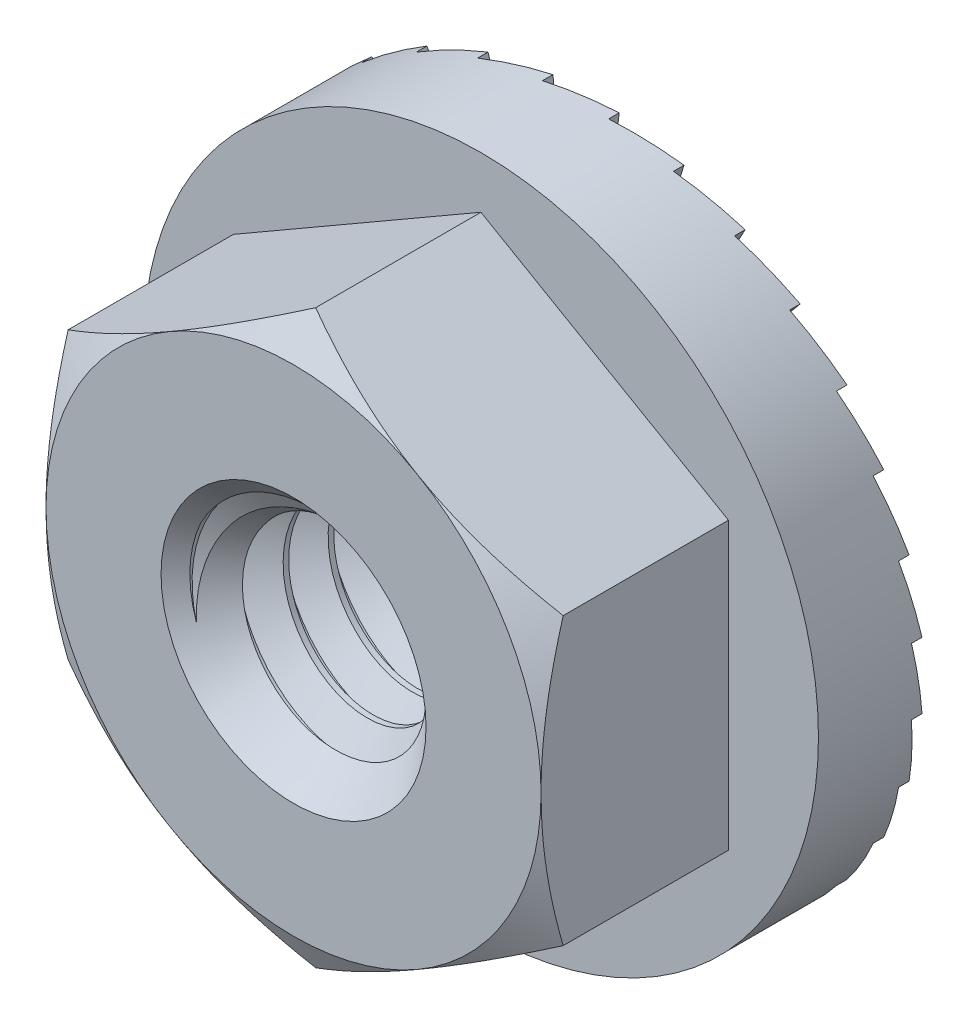
SolidWorks part; units mm, degrees
ref_plane "Front Plane" through (0, 0, 0) normal (0, 0, 1) x (1, 0, 0)
ref_plane "Top Plane" through (0, 0, 0) normal (0, 1, 0) x (1, 0, 0)
ref_plane "Right Plane" through (0, 0, 0) normal (1, 0, 0) x (0, 0, -1)
sketch "Sketch1" plane through (0, 0, 0) normal (0, 0, 1) x (1, 0, 0)
  line L1 (0, 5.041) -> (-4.3656, 2.5205)
  line L2 (-4.3656, 2.5205) -> (-4.3656, -2.5205)
  line L3 (-4.3656, -2.5205) -> (0, -5.041)
  line L4 (0, -5.041) -> (4.3656, -2.5205)
  line L5 (4.3656, -2.5205) -> (4.3656, 2.5205)
  line L6 (4.3656, 2.5205) -> (0, 5.041)
  circle A0 centre (0, 0) radius 4.3656 construction
  dimension "Hex" = 8.7312
extrude "Extrude1" add sketch "Sketch1" against normal blind 5.1594
sketch "Sketch13" plane through (0, 0, -5.1594) normal (0, 0, -1) x (-1, 0, 0)
  circle A0 centre (0, 0) radius 5.9531
  dimension "Flange od" = 11.9062
extrude "Extrude3" add sketch "Sketch13" against normal blind 1.8542
sketch "Sketch2" plane through (0, 0, 0) normal (0, 0, 1) x (1, 0, 0)
  circle A0 centre (0, 0) radius 4.3656 construction
  circle A1 centre (0, 0) radius 4.3656
extrude "Cut-Extrude1" cut sketch "Sketch2" against normal through all draft 60 flip side to cut
sketch "Sketch4" plane through (0, 0, 0) normal (0, 0, 1) x (1, 0, 0)
  circle A0 centre (0, 0) radius 2.0828
  dimension "Thread Dia" = 4.1656
extrude "Cut-Extrude3" cut sketch "Sketch4" against normal through all
sketch "Sketch7" plane through (0, 0, 0) normal (0, 0, 1) x (1, 0, 0)
  circle A4 centre (0, 0) radius 2.3368
  circle A5 centre (0, 0) radius 2.3368
  dimension "D1" = 0.254
sketch "Sketch8" plane through (0, 0, -5.1594) normal (0, 0, -1) x (-1, 0, 0)
  circle A1 centre (0, 0) radius 2.3368
  circle A2 centre (0, 0) radius 2.3368 construction
sketch "Sketch5" plane through (0, 0, 0) normal (0, 0, 1) x (1, 0, 0)
  circle A0 centre (0, 0) radius 2.0828 construction
  circle A1 centre (0, 0) radius 2.0828
curve "Helix/Spiral1" pitch 0.7937 height 5.9531 turns 7.5 parameters "pitch"=0.7937
sketch "Sketch9" plane through (0, 0, 0) normal (1, 0, 0) x (0, 0, -1)
  line L0 (-0.3969, 2.0828) -> (-0.2977, 2.0828)
  line L1 (-0.2977, 2.0828) -> (0, 1.5672)
  line L2 (-0.3969, 2.0828) -> (-0.6945, 1.5672)
  line L3 (-0.6945, 1.5672) -> (0, 1.5672)
  line L4 (-0.3473, 2.0828) -> (-0.3473, 1.5672) construction
  line L5 (-0.5457, 1.825) -> (-0.1488, 1.825) construction
  line L7 (0, 1.5672) -> (0, 2.0828) construction
  line L8 (0, 2.0828) -> (0, -2.0828) construction
  dimension "D1" = 0.0992
  dimension "D2" = 0.3969
  dimension "D3" = 60
sketch "Sketch12" plane through (0, 0, 0) normal (0, 0, 1) x (1, 0, 0)
  circle A0 centre (0, 0) radius 1.5672
  circle A1 centre (0, 0) radius 2.0828 construction
  circle A2 centre (0, 0) radius 2.0828
extrude "Extrude2" add sketch "Sketch12" against normal up to surface (5.1594 mm away)
sweep "Cut-Sweep1" cut profiles "Sketch9" path "Helix/Spiral1"
extrude "Cut-Extrude6" cut sketch "Sketch7" against normal through all draft 45
extrude "Cut-Extrude7" cut sketch "Sketch8" against normal through all draft 45
sketch "Sketch14" plane through (0, 0, -5.1594) normal (0, 0, -1) x (-1, 0, 0)
  circle A4 centre (0, 0) radius 4.3688
  circle A5 centre (0, 0) radius 4.3688
  dimension "D1" = 2.032
extrude "Cut-Extrude8" cut sketch "Sketch14" against normal blind 0.1854 flip side to cut
sketch "Sketch15" plane through (0, 0, -4.974) normal (0, 0, -1) x (-1, 0, 0)
  line L0 (-0.4282, 4.3478) -> (-0.5835, 5.9245)
  line L1 (0.4282, 4.3478) -> (0.5835, 5.9245)
  line L2 (0, 0) -> (0.4282, 4.3478) construction
  line L3 (0, 0) -> (-0.4282, 4.3478) construction
  circle A0 centre (0, 0) radius 5.9531 construction
  circle A1 centre (0, 0) radius 4.3688 construction
  arc A2 (0.5835, 5.9245) -> (-0.5835, 5.9245) centre (0, 0) ccw
  arc A3 (0.4282, 4.3478) -> (-0.4282, 4.3478) centre (0, 0) ccw
  dimension "D1" = 11.25
extrude "Extrude4" add sketch "Sketch15" along normal up to surface (0.1854 mm away) separate body up to face at (-2.3368, 0, -5.1594)
sketch "Sketch16" plane through (0, 0, 0) normal (0, 1, 0) x (1, 0, 0)
  line L0 (-0.5835, 4.974) -> (0.5835, 5.1594)
  line L4 (-0.5835, 4.974) -> (0.5835, 4.974)
  line L5 (0.5835, 4.974) -> (0.5835, 5.1594)
  line L6 (0.5835, 5.1594) -> (-0.5835, 5.1594)
  line L7 (-0.5835, 5.1594) -> (-0.5835, 4.974)
  line L8 (-0.5835, 4.974) -> (0.5835, 4.974) construction
  line L9 (0.5835, 4.974) -> (0.5835, 5.1594) construction
  line L10 (0.5835, 5.1594) -> (-0.5835, 5.1594)
  line L11 (-0.5835, 5.1594) -> (-0.5835, 4.974)
  dimension "D1" = 0
extrude "Cut-Extrude9" cut sketch "Sketch16" along normal through all
pattern_circular "CirPattern1" count 32 over 360 about axis through (0, 0, 0) along (0, 0, 1) of bodies 119
combine bodies "Combine1" operation type add bodies to combine 117 119 120 121 122 123 124 125 126 127 128 129 130 131 132 133 134 135 136 137 139 140 141 142 143 144 145 146 147 148 149 150 151
sketch "Sketch17" plane through (0, 0, 0) normal (1, 0, 0) x (0, 0, -1)
  line L0 (5.1594, 5.9531) -> (5.1594, -5.9531) construction
  line L1 (3.3052, 5.9531) -> (3.3052, -5.9531) construction
  dimension "D1" = 1.8542
sketch "Sketch18" plane through (0, 0, -3.3052) normal (0, 0, 1) x (1, 0, 0)
  circle A0 centre (0, 0) radius 5.9531
  circle A1 centre (0, 0) radius 5.9531 construction
equation "\"D2@Sketch9\" = \"pitch@Helix/Spiral1\"*.5"
equation "\"D3@Helix/Spiral1\" = \"pitch@Helix/Spiral1\"+\"Height@Extrude1\""
equation "\"D1@Sketch9\" = \"pitch@Helix/Spiral1\"*.125"
equation "\"D1@Cut-Extrude8\" = \"flange thickness@Extrude3\"*.1"
equation "\"D1@Sketch17\" = \"flange thickness@Extrude3\""
